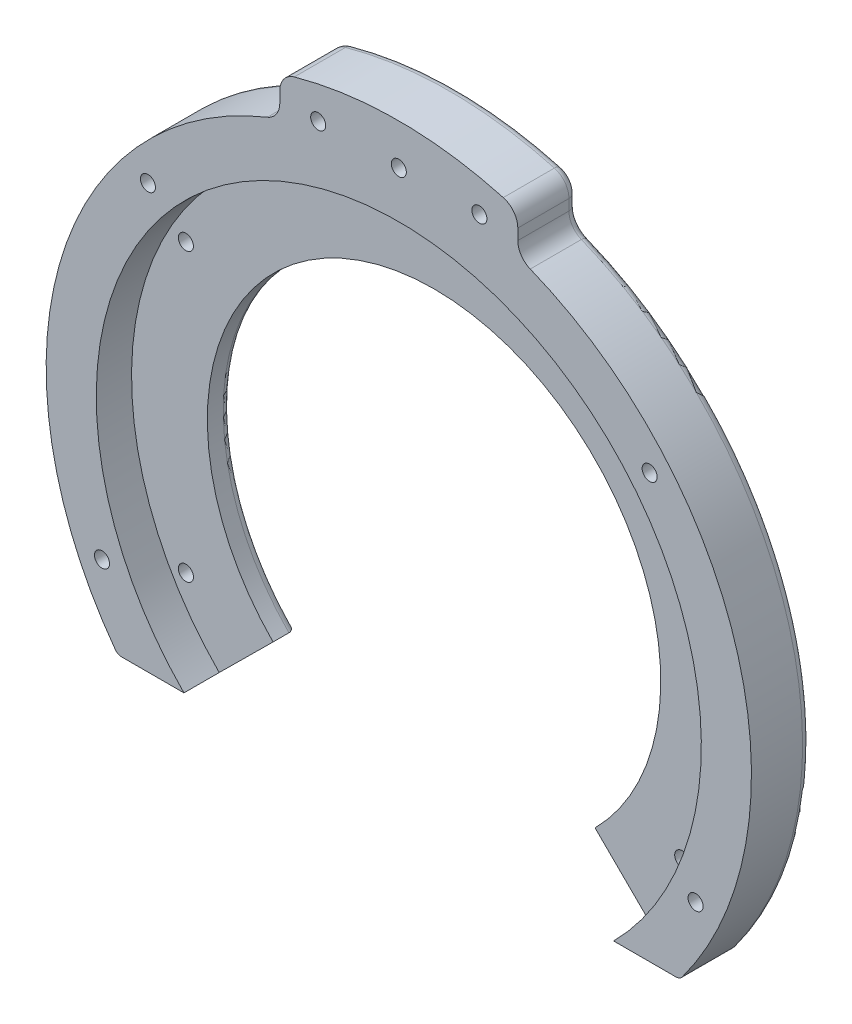
SolidWorks part; units mm, degrees
material "ABS"
ref_plane "Front Plane" through (0, 0, 0) normal (0, 0, 1) x (1, 0, 0)
ref_plane "Top Plane" through (0, 0, 0) normal (0, 1, 0) x (1, 0, 0)
ref_plane "Right Plane" through (0, 0, 0) normal (1, 0, 0) x (0, 0, -1)
sketch "Sketch1" plane through (0, 0, 0) normal (0, 0, 1) x (1, 0, 0)
  line L0 (0, 0) -> (0, 98.2852) construction
  line L1 (0, 98.2852) -> (-30, 98.2852) construction
  line L2 (0, 98.2852) -> (30, 98.2852) construction
  line L3 (30, 98.2852) -> (30, 83.6852) construction
  line L4 (-30, 98.2852) -> (-30, 83.6852) construction
  line L5 (-30, 83.6852) -> (-30, 93.5948)
  line L6 (30, 83.6852) -> (30, 93.5948)
  line L7 (0, 0) -> (-62.2819, 0) construction
  line L8 (0, 0) -> (62.2819, 0) construction
  line L9 (-62.2819, 0) -> (-62.2819, 44.0124) construction
  line L10 (62.2819, 0) -> (62.2819, 44.0124) construction
  line L11 (0, 0) -> (-62.2819, 44.0124) construction
  line L12 (0, 0) -> (62.2819, 44.0124) construction
  line L13 (0, 0) -> (-63.1328, -62.5897) construction
  line L14 (0, 0) -> (63.1328, -62.5897) construction
  line L15 (-54.1589, -53.693) -> (-70.8539, -53.693)
  line L16 (54.1589, -53.693) -> (70.8539, -53.693)
  line L17 (-54.1589, -53.693) -> (-40.5853, -40.2362)
  line L18 (54.1589, -53.693) -> (40.5853, -40.2362)
  circle A0 centre (0, 0) radius 88.9
  circle A1 centre (0, 0) radius 76.2635
  circle A2 centre (0, 0) radius 57.15
  arc A3 (30, 93.5948) -> (-30, 93.5948) centre (0, 0) ccw
  point P16 (-54.1589, -53.693)
  point P19 (54.1589, -53.693)
  dimension "D1" = 177.8
  dimension "D2" = 152.527
  dimension "D3" = 114.3
  dimension "D4" = 30
  dimension "D5" = 30
  dimension "D6" = 14.6
  dimension "D7" = 54.752
  dimension "D8" = 54.752
  dimension "D9" = 80
  dimension "D10" = 80
extrude "Boss-Extrude1" add sketch "Sketch1" along normal blind 6 contours A2 L18 A1 L17 | A1 L16 A0 L15 region at (0, 86.6208, 0) region at (-28.2697, 68.6682, 0)
extrude "Boss-Extrude2" add sketch "Sketch1<3>" along normal blind 14.89 contours A1 L16 A0 L15 region at (0, 86.6208, 0)
sketch "Sketch1<3>" plane through (0, 0, 0) normal (0, 0, 1) x (1, 0, 0) same geometry as "Sketch1"
extrude "Boss-Extrude3" add sketch "Sketch1<4>" along normal blind 14.89 contours L6 A3 L5 A0 region at (0, 91.936, 0)
sketch "Sketch1<4>" plane through (0, 0, 0) normal (0, 0, 1) x (1, 0, 0) same geometry as "Sketch1"
hole_wizard "CBORE for #6 Socket Head Cap Screw1" positions "3DSketch1" profile "Sketch2" counterbore size "#6" standard "ANSI Inch" end condition through all
sketch3d "3DSketch1"
  line L0 (70.8539, -53.693, 0) -> (-70.8539, -53.693, 0) construction
  line L1 (0, 0, 0) -> (0, -53.693, 0) construction
  line L3 (0, 0, 0) -> (68.1014, 57.1438, 0) construction
  line L4 (0, 0, 0) -> (80.5708, -37.5708, 0) construction
  line L5 (0, 0, 0) -> (-80.5708, -37.5708, 0) construction
  line L6 (0, 0, 0) -> (-68.1014, 57.1438, 0) construction
  arc A0 (70.8539, -53.693, 0) -> (30, 83.6852, 0) centre (0, 0, 0) ccw construction
  arc A1 (-30, 83.6852, 0) -> (-70.8539, -53.693, 0) centre (0, 0, 0) ccw construction
  circle A3 centre (0, 0, 0) radius 82.55
  point P0 (74.8157, -34.8871, 0)
  point P2 (63.237, 53.0621, 0)
  point P4 (-63.237, 53.0621, 0)
  point P6 (-74.8157, -34.8871, 0)
  point P23 (0, 0, 88.9)
  point P32 (0, 0, 88.9)
  point P42 (0, 0, 82.55)
  dimension "D5" = 165.1
  dimension "D1" = 65
  dimension "D2" = 65
  dimension "D3" = 130
  dimension "D4" = 130
sketch "Sketch2" plane through (74.8157, -34.8871, 0) normal (1, 0, 0) x (0, 1, 0)
  line L0 (0, 0) -> (0, 14.89)
  line L1 (0, 14.89) -> (1.8986, 14.89)
  line L3 (1.8986, 14.89) -> (1.8986, 3.5052)
  line L4 (1.8986, 3.5052) -> (3.5725, 3.5052)
  line L5 (3.5725, 3.5052) -> (3.5725, 0)
  line L7 (3.5725, 0) -> (0, 0)
  line L11 (0, -6.35) -> (0, 107.95) construction
  dimension "Thru Hole Dia." = 3.7973
  dimension "Thru Hole Depth" = 14.89
  dimension "C'Bore Dia." = 7.145
  dimension "C'Bore Depth" = 3.5052
hole_wizard "#6 Clearance Hole1" positions "3DSketch2" profile "Sketch4" hole size "#6" standard "ANSI Inch" end condition through all
sketch3d "3DSketch2"
  line L1 (0, 0, 14.89) -> (0, 0, 0) construction
  line L2 (0, 0, 14.89) -> (0, 0, 6) construction
  line L3 (0, 0, 14.89) -> (0, 95, 14.89) construction
  line L4 (0, 88, 14.89) -> (-20.32, 88, 14.89) construction
  line L5 (0, 88, 14.89) -> (20.32, 88, 14.89) construction
  circle A3 centre (0, 0, 14.89) radius 95
  circle A4 centre (0, 0, 14.89) radius 85
  circle A5 centre (0, 0, 14.89) radius 88
  point P0 (0, 88, 14.89)
  point P2 (20.32, 88, 14.89)
  point P4 (-20.32, 88, 14.89)
  point P23 (0, 0, 109.89)
  point P33 (0, 0, 99.89)
  point P37 (0, 0, 102.89)
  dimension "D1" = 190
  dimension "D2" = 170
  dimension "D3" = 176
  dimension "D4" = 20.32
  dimension "D5" = 20.32
sketch "Sketch4" plane through (0, 88, 14.89) normal (1, 0, 0) x (0, -1, 0)
  line L0 (0, 0) -> (0, 14.89)
  line L1 (0, 14.89) -> (1.8986, 14.89)
  line L2 (1.8986, 14.89) -> (1.8986, 0)
  line L5 (1.8986, 0) -> (0, 0)
  line L11 (0, -6.35) -> (0, 107.95) construction
  dimension "Thru Hole Dia." = 3.7973
  dimension "Thru Hole Depth" = 14.89
fillet "Fillet1" radius 5 2 edges at (30, 83.6852, 7.445) (-30, 83.6852, 7.445) tangent propagation no
fillet "Fillet2" radius 5 2 edges at (-30, 93.5948, 7.445) (30, 93.5948, 7.445)
fillet "Fillet3" radius 2 16 edges at (-85.6749, 23.7281, 0) (-30.8576, 84.3331, 0) (-30, 88.5031, 0) (-28.9812, 92.8977, 0) (0, 98.2852, 0) (28.9812, 92.8977, 0) (30, 88.5031, 0) (30.8576, 84.3331, 0) (85.6749, 23.7281, 0) (0, 57.15, 0) (70.8539, -53.693, 7.445) (62.5064, -53.693, 0) (47.3721, -46.9646, 0) (-70.8539, -53.693, 7.445) (-47.3721, -46.9646, 0) (-62.5064, -53.693, 0)
hole_wizard "#6 Clearance Hole2" positions "3DSketch3" profile "Sketch5" hole size "#6" standard "ANSI Inch" end condition through all
sketch3d "3DSketch3"
  line L0 (0, 0, 0) -> (0, 72.2376, 0) construction
  line L1 (0, 0, 0) -> (36.1188, 62.5596, 0) construction
  line L2 (0, 0, 0) -> (72.2376, 0, 0) construction
  line L3 (0, 0, 0) -> (62.5596, -36.1188, 0) construction
  line L4 (0, 0, 0) -> (-36.1188, 62.5596, 0) construction
  line L5 (0, 0, 0) -> (-62.5596, 36.1188, 0) construction
  line L6 (0, 0, 0) -> (-72.2376, 0, 0) construction
  line L7 (0, 0, 0) -> (-62.5596, -36.1188, 0) construction
  line L8 (0, 0, 0) -> (62.5596, 36.1188, 0) construction
  circle A0 centre (0, 0, 0) radius 72.2376
  point P0 (62.5596, -36.1188, 0)
  point P4 (62.5596, 36.1188, 0)
  point P8 (0, 72.2376, 0)
  point P12 (-62.5596, 36.1188, 0)
  point P16 (-62.5596, -36.1188, 0)
  point P21 (0, 0, 72.2376)
  dimension "D1" = 144.4752
  dimension "D2" = 30
  dimension "D3" = 30
  dimension "D4" = 30
  dimension "D5" = 30
  dimension "D6" = 30
  dimension "D7" = 30
  dimension "D8" = 30
  dimension "D9" = 30
sketch "Sketch5" plane through (62.5596, -36.1188, 0) normal (1, 0, 0) x (0, 1, 0)
  line L0 (0, 0) -> (0, 14.89)
  line L1 (0, 14.89) -> (1.8986, 14.89)
  line L2 (1.8986, 14.89) -> (1.8986, 0)
  line L5 (1.8986, 0) -> (0, 0)
  line L11 (0, -6.35) -> (0, 107.95) construction
  dimension "Thru Hole Dia." = 3.7973
  dimension "Thru Hole Depth" = 14.89
